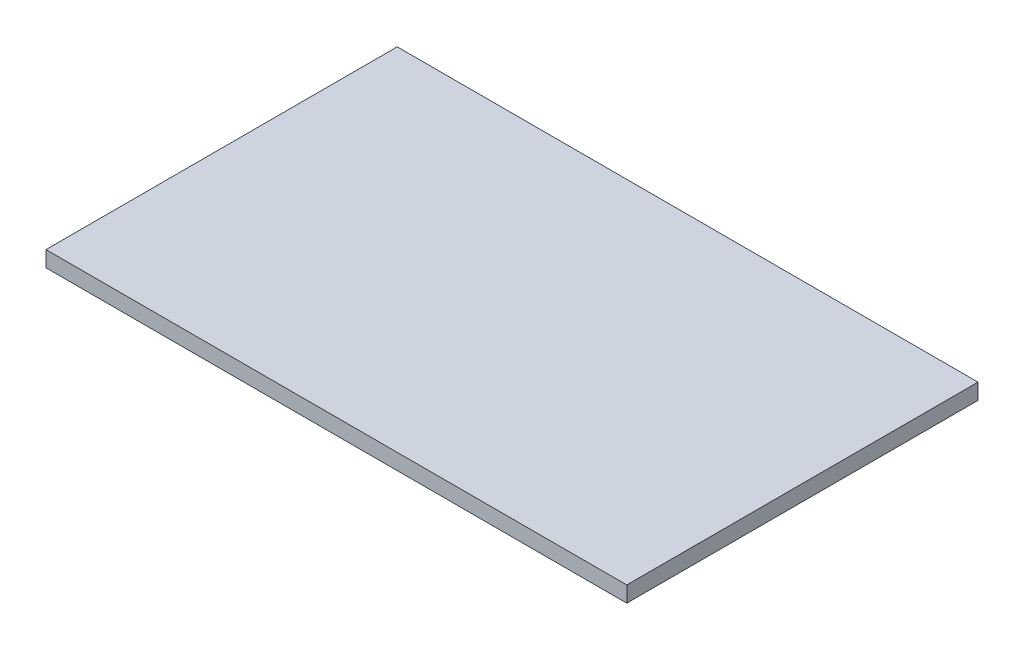
SolidWorks part; units mm, degrees
ref_plane "Front Plane" through (0, 0, 0) normal (0, 0, 1) x (1, 0, 0)
ref_plane "Top Plane" through (0, 0, 0) normal (0, 1, 0) x (1, 0, 0)
ref_plane "Right Plane" through (0, 0, 0) normal (1, 0, 0) x (0, 0, -1)
sketch "Sketch1" plane through (0, 0, 0) normal (0, 1, 0) x (1, 0, 0)
  line L1 (-46.6452, -28.2069) -> (46.6452, -28.2069)
  line L2 (-46.6452, -28.2069) -> (-46.6452, 28.2069)
  line L3 (-46.6452, 28.2069) -> (46.6452, 28.2069)
  line L4 (46.6452, -28.2069) -> (46.6452, 28.2069)
  line L5 (-46.6452, -28.2069) -> (46.6452, 28.2069) construction
  line L6 (-46.6452, 28.2069) -> (46.6452, -28.2069) construction
  point P0 (0, 0)
extrude "Boss-Extrude1" add sketch "Sketch1" along normal blind 2.54
